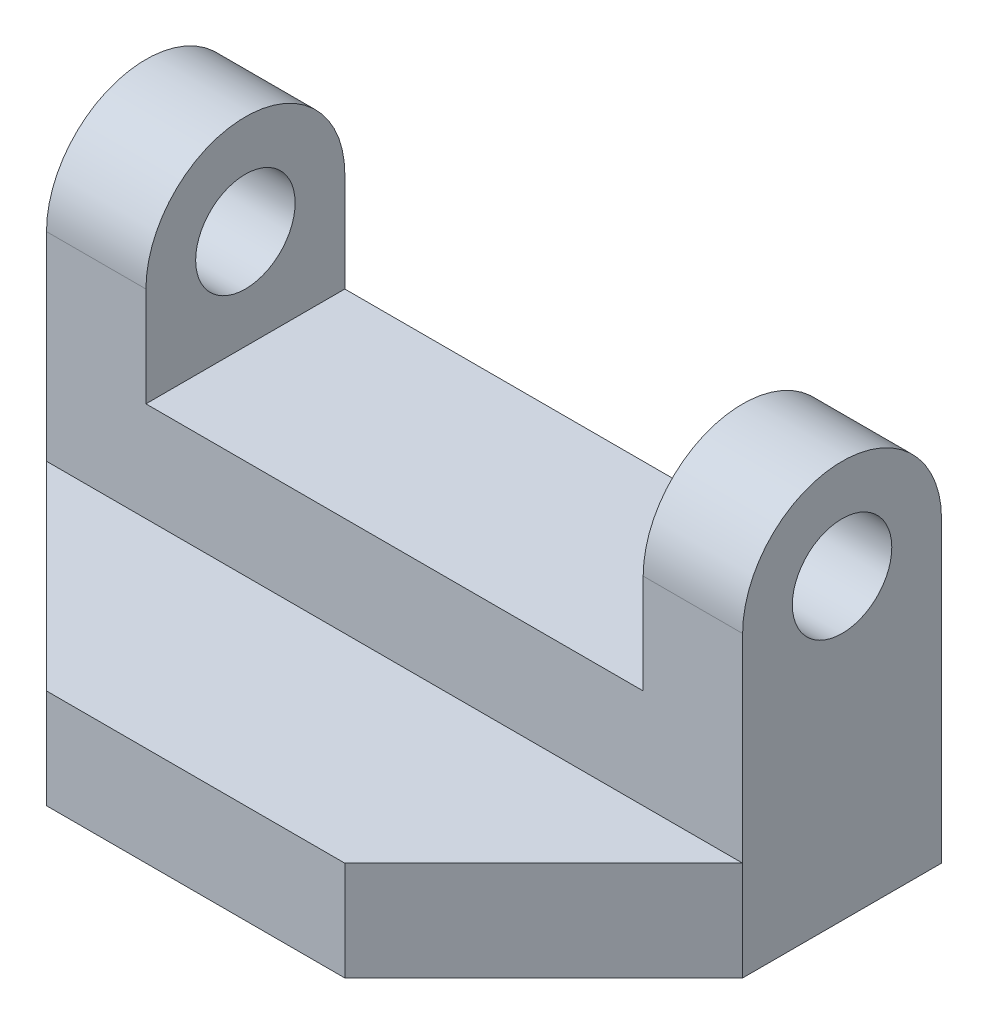
SolidWorks part; units mm, degrees
ref_plane "Front Plane" through (0, 0, 0) normal (0, 0, 1) x (1, 0, 0)
ref_plane "Top Plane" through (0, 0, 0) normal (0, 1, 0) x (1, 0, 0)
ref_plane "Right Plane" through (0, 0, 0) normal (1, 0, 0) x (0, 0, -1)
sketch "Sketch1" plane through (0, 0, 0) normal (0, 1, 0) x (1, 0, 0)
  line L0 (0, 0) -> (70, 0)
  line L1 (70, 0) -> (50, -20)
  line L2 (50, -20) -> (20, -20)
  line L3 (20, -20) -> (0, 0)
  line L4 (0, 0) -> (0, 20)
  line L5 (0, 20) -> (70, 20)
  line L6 (70, 20) -> (70, 0)
  line L7 (10, 20) -> (10, 0)
  line L8 (60, 20) -> (60, 0)
  dimension "D1" = 70
  dimension "D2" = 30
  dimension "D3" = 20
  dimension "D4" = 40
  dimension "D5" = 20
  dimension "D6" = 10
  dimension "D7" = 10
extrude "Boss-Extrude1" add sketch "Sketch1" along normal blind 10 contours L3 L2 L1 L0 region at (35, 0, 8.6667)
extrude "Boss-Extrude2" add sketch "Sketch1<3>" along normal blind 20 contours L8 L5 L7 L0 region at (35, 0, -10)
sketch "Sketch1<3>" plane through (0, 0, 0) normal (0, 1, 0) x (1, 0, 0) same geometry as "Sketch1"
extrude "Boss-Extrude3" add sketch "Sketch1<4>" along normal blind 40 contours L5 L8 L0 L6 | L7 L5 L4 L0 region at (5, 0, -10) region at (65, 0, -10)
sketch "Sketch1<4>" plane through (0, 0, 0) normal (0, 1, 0) x (1, 0, 0) same geometry as "Sketch1"
fillet "Fillet1" 2 edges at (65, 40, 0) (65, 40, -20) type full round first side face at (35, 27.5, 0) second side face at (35, 25, -20) middle face at (65, 40, -10)
fillet "Fillet2" 2 edges at (5, 40, -20) (5, 40, 0) type full round first side face at (35, 22.5, -20) second side face at (35, 25, 0) middle face at (5, 40, -10)
sketch "Sketch2" plane through (60, 0, 0) normal (-1, 0, 0) x (0, 0, 1)
  circle A0 centre (-10, 30) radius 5
  arc A1 (0, 30) -> (-20, 30) centre (-10, 30) ccw construction
  dimension "D1" = 10
extrude "Cut-Extrude1" cut sketch "Sketch2" against normal up to next
extrude "Cut-Extrude2" cut sketch "Sketch2<2>" against normal up to next from surface starting at face at (0, 16, -8)
sketch "Sketch2<2>" plane through (60, 0, 0) normal (-1, 0, 0) x (0, 0, 1) same geometry as "Sketch2"
